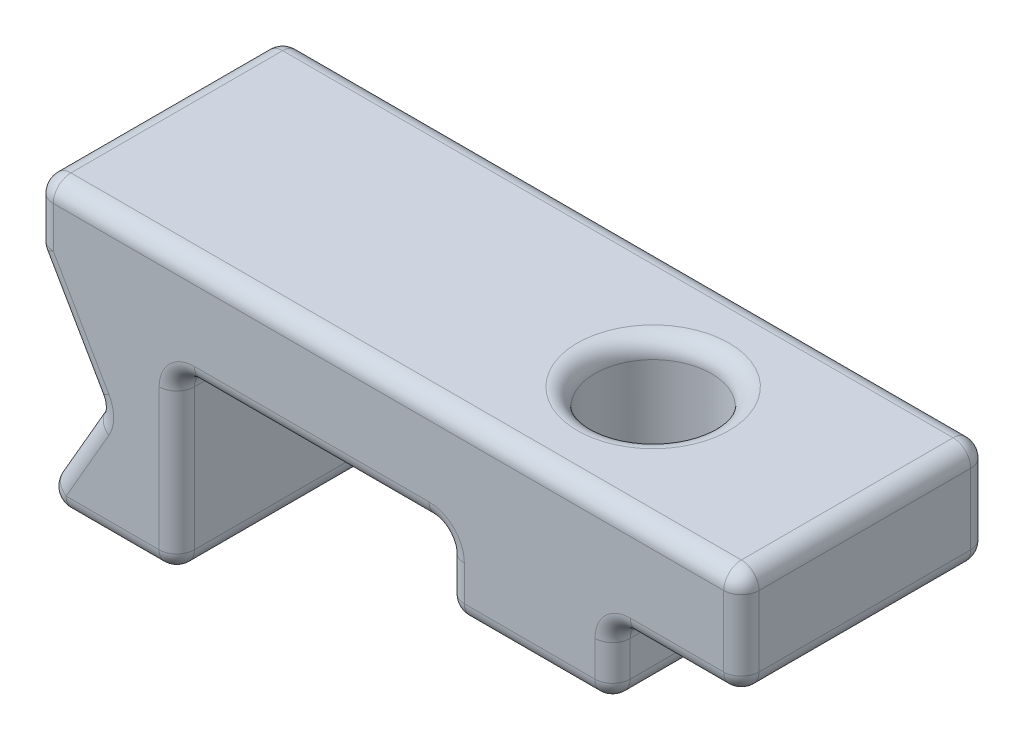
SolidWorks part; units mm, degrees
ref_plane "Plan de face" through (0, 0, 0) normal (0, 0, 1) x (1, 0, 0)
ref_plane "Plan de dessus" through (0, 0, 0) normal (0, 1, 0) x (1, 0, 0)
ref_plane "Plan de droite" through (0, 0, 0) normal (1, 0, 0) x (0, 0, -1)
sketch "Esquisse1" plane through (0, 0, 0) normal (0, 0, 1) x (1, 0, 0)
  line L0 (-6, 0) -> (-2.35, 0)
  line L1 (-2.35, -2) -> (2.35, -2)
  line L2 (-6, 0) -> (-6, 3)
  line L3 (-6, 3) -> (6, 3)
  line L4 (6, 0) -> (6, 3)
  line L5 (-6, 0) -> (6, 0) construction
  line L7 (-2.35, 0) -> (-2.35, -2)
  line L8 (6, 0) -> (2.35, 0)
  line L9 (2.35, 0) -> (2.35, -2)
  point P0 (0, 0)
  dimension "D1" = 12
  dimension "D2" = 4.7
  dimension "D3" = 3
  dimension "D4" = 2
extrude "Boss.-Extru.1" add sketch "Esquisse1" along normal mid plane 7
sketch "Esquisse2" plane through (0, 3, 0) normal (0, 1, 0) x (1, 0, 0)
  circle A0 centre (0, 0) radius 1.65
  dimension "D1" = 3.3
extrude "Enlèv. mat.-Extru.1" cut sketch "Esquisse2" against normal through all
sketch "Esquisse3" plane through (-6, 0, 0) normal (-1, 0, 0) x (0, 0, 1)
  line L1 (-3.5, 3) -> (3.5, 3)
  line L2 (-3.5, 3) -> (-3.5, 0)
  line L3 (-3.5, 0) -> (3.5, 0)
  line L4 (3.5, 3) -> (3.5, 0)
extrude "Boss.-Extru.2" add sketch "Esquisse3" along normal blind 8
sketch "Esquisse6" plane through (0, 0, 0) normal (0, -1, 0) x (1, 0, 0)
  line L0 (-14, -3.5) -> (-2.35, -3.5) construction
  line L1 (-14, 3.5) -> (-10, 3.5)
  line L2 (-14, 3.5) -> (-14, -3.5)
  line L3 (-14, -3.5) -> (-10, -3.5)
  line L4 (-10, 3.5) -> (-10, -3.5)
  dimension "D1" = 4
extrude "Boss.-Extru.4" add sketch "Esquisse6" along normal blind 5
sketch "Esquisse7" plane through (0, 0, 3.5) normal (0, 0, 1) x (1, 0, 0)
  line L0 (-14, 1.2) -> (-14, -5) construction
  line L1 (-14, 1.2) -> (-12.2102, -1.9)
  line L2 (-12.2102, -1.9) -> (-14, -5)
  line L3 (-14, 1.2) -> (-14, -5)
  line L6 (-10, 0) -> (-2.35, 0) construction
  point P6 (-14, -1.9)
  dimension "D1" = 120
  dimension "D2" = 1.9
extrude "Enlèv. mat.-Extru.3" cut sketch "Esquisse7" against normal through all
fillet "Congé2" radius 0.5 38 edges at (-4, 3, -3.5) (6, 3, 0) (6, 1.5, -3.5) (2.35, -1, -3.5) (-10, -2.5, -3.5) (-10, -5, 0) (-12, -5, -3.5) (0, 3, 1.65) (2.35, 0, 0) (6, 0, 0) (4.175, 0, -3.5) (2.35, -2, 0) (0, -2, -3.5) (0, -2, 1.65) (-2.35, -2, 0) (-2.35, -1, -3.5) (-2.35, 0, 0) (-6.175, 0, -3.5) (-10, 0, 0) (-14, -5, 0) (-13.1051, -3.45, -3.5) (-12.2102, -1.9, 0) (-13.1051, -0.35, -3.5) (6, 1.5, 3.5) (4.175, 0, 3.5) (2.35, -1, 3.5) (0, -2, 3.5) (-2.35, -1, 3.5) (-6.175, 0, 3.5) (-10, -2.5, 3.5) (-12, -5, 3.5) (-13.1051, -3.45, 3.5) (-13.1051, -0.35, 3.5) (-4, 3, 3.5) (-14, 3, 0) (-14, 2.1, -3.5) (-14, 1.2, 0) (-14, 2.1, 3.5)
